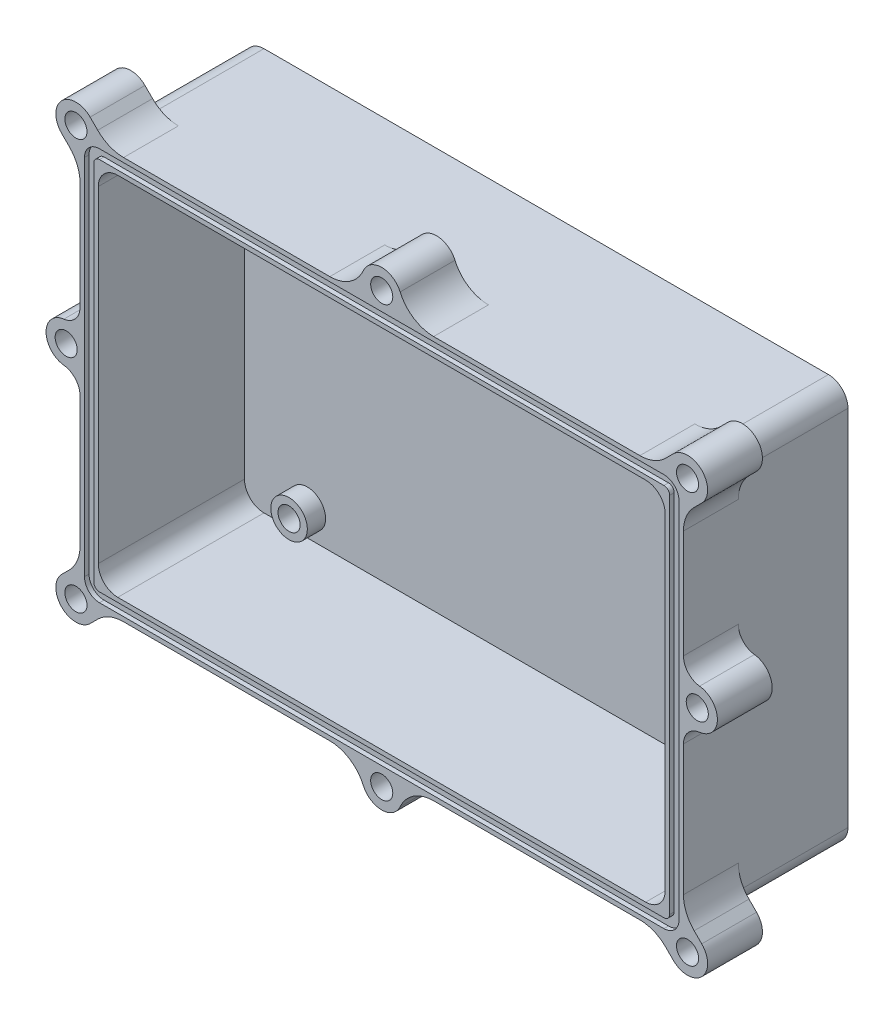
SolidWorks part; units mm, degrees
material "Custom Plastic"
ref_plane "X-Y Datum" through (0, 0, 0) normal (0, 0, 1) x (1, 0, 0)
ref_plane "X-Z Datum" through (0, 0, 0) normal (0, 1, 0) x (1, 0, 0)
ref_plane "Y-Z Datum" through (0, 0, 0) normal (1, 0, 0) x (0, 0, -1)
sketch "Sketch1" plane through (0, 0, 0) normal (0, 0, 1) x (1, 0, 0)
  line L1 (-82.55, 55) -> (82.55, 55)
  line L2 (-82.55, 55) -> (-82.55, -55)
  line L3 (-82.55, -55) -> (82.55, -55)
  line L4 (82.55, 55) -> (82.55, -55)
  line L5 (-82.55, 55) -> (82.55, -55) construction
  line L6 (-82.55, -55) -> (82.55, 55) construction
  point P0 (0, 0)
  dimension "D1" = 165.1
  dimension "D2" = 110
extrude "Boss-Extrude1" add sketch "Sketch1" along normal blind 45
shell "Shell1" thickness 5 removed face at (0, 0, 45)
fillet "Fillet1" radius 5.334 8 edges at (-77.55, -50, 25) (-82.55, -55, 22.5) (82.55, -55, 22.5) (77.55, -50, 25) (82.55, 55, 22.5) (77.55, 50, 25) (-82.55, 55, 22.5) (-77.55, 50, 25)
sketch "Sketch2" plane through (0, 0, 45) normal (0, 0, 1) x (1, 0, 0)
  line L20 (-77.216, -53.7827) -> (77.216, -53.7827)
  line L21 (81.3327, -49.666) -> (81.3327, 49.666)
  line L22 (77.216, 53.7827) -> (-77.216, 53.7827)
  line L23 (-81.3327, 49.666) -> (-81.3327, -49.666)
  line L24 (-77.216, -52.5) -> (77.216, -52.5)
  line L25 (80.05, -49.666) -> (80.05, 49.666)
  line L26 (77.216, 52.5) -> (-77.216, 52.5)
  line L27 (-80.05, 49.666) -> (-80.05, -49.666)
  line L28 (-77.216, -52.5) -> (77.216, -52.5) construction
  line L29 (80.05, -49.666) -> (80.05, 49.666) construction
  line L30 (77.216, 52.5) -> (-77.216, 52.5) construction
  line L31 (-80.05, 49.666) -> (-80.05, -49.666) construction
  line L32 (-78.7673, 49.666) -> (-78.7673, -49.666)
  line L33 (-77.216, -51.2173) -> (77.216, -51.2173)
  line L34 (78.7673, -49.666) -> (78.7673, 49.666)
  line L35 (77.216, 51.2173) -> (-77.216, 51.2173)
  arc A16 (77.216, -53.7827) -> (81.3327, -49.666) centre (77.216, -49.666) ccw
  arc A17 (81.3327, 49.666) -> (77.216, 53.7827) centre (77.216, 49.666) ccw
  arc A18 (-77.216, 53.7827) -> (-81.3327, 49.666) centre (-77.216, 49.666) ccw
  arc A19 (-81.3327, -49.666) -> (-77.216, -53.7827) centre (-77.216, -49.666) ccw
  arc A20 (-80.05, -49.666) -> (-77.216, -52.5) centre (-77.216, -49.666) ccw
  arc A21 (77.216, -52.5) -> (80.05, -49.666) centre (77.216, -49.666) ccw
  arc A22 (80.05, 49.666) -> (77.216, 52.5) centre (77.216, 49.666) ccw
  arc A23 (-77.216, 52.5) -> (-80.05, 49.666) centre (-77.216, 49.666) ccw
  arc A24 (-80.05, -49.666) -> (-77.216, -52.5) centre (-77.216, -49.666) ccw construction
  arc A25 (77.216, -52.5) -> (80.05, -49.666) centre (77.216, -49.666) ccw construction
  arc A26 (80.05, 49.666) -> (77.216, 52.5) centre (77.216, 49.666) ccw construction
  arc A27 (-77.216, 52.5) -> (-80.05, 49.666) centre (-77.216, 49.666) ccw construction
  arc A28 (-77.216, 51.2173) -> (-78.7673, 49.666) centre (-77.216, 49.666) ccw
  arc A29 (-78.7673, -49.666) -> (-77.216, -51.2173) centre (-77.216, -49.666) ccw
  arc A30 (77.216, -51.2173) -> (78.7673, -49.666) centre (77.216, -49.666) ccw
  arc A31 (78.7673, 49.666) -> (77.216, 51.2173) centre (77.216, 49.666) ccw
  dimension "D1" = 2.5
  dimension "D2" = 1.2827
  dimension "D3" = 1.2827
extrude "Cut-Extrude1" cut sketch "Sketch2" against normal blind 1.2446
sketch "Sketch3" plane through (0, 0, 45) normal (0, 0, 1) x (1, 0, 0)
  line L0 (77.216, 49.666) -> (80.9877, 53.4377)
  line L1 (80.9877, 53.4377) -> (83.6625, 56.1125)
  line L2 (79.7734, 60.0016) -> (74.7718, 55)
  line L3 (77.216, 55) -> (-77.216, 55) construction
  line L4 (82.55, -49.666) -> (82.55, 49.666) construction
  line L5 (82.55, -49.666) -> (82.55, 49.666)
  line L6 (77.216, 55) -> (-77.216, 55)
  line L7 (87.5516, 52.2234) -> (82.55, 47.2218)
  arc A0 (82.55, 49.666) -> (77.216, 55) centre (77.216, 49.666) ccw construction
  circle A1 centre (83.6625, 56.1125) radius 3.025
  circle A2 centre (83.6625, 56.1125) radius 5.5
  arc A3 (81.3327, 49.666) -> (77.216, 53.7827) centre (77.216, 49.666) ccw construction
  arc A4 (82.55, 49.666) -> (77.216, 55) centre (77.216, 49.666) ccw
  point P6 (87.5516, 52.2234)
  point P10 (80.1269, 52.5769)
  dimension "D1" = 6.05
  dimension "D2" = 11
  dimension "D3" = 5
extrude "Boss-Extrude2" add sketch "Sketch3" against normal blind 15
sketch "Sketch4" plane through (0, 0, 45) normal (0, 0, 1) x (1, 0, 0)
  line L0 (87.5516, 52.2234) -> (82.55, 47.2218) construction
  line L1 (79.7734, 60.0016) -> (74.7718, 55) construction
  line L2 (77.216, 49.666) -> (80.9877, 53.4377) construction
  line L3 (80.9877, 53.4377) -> (83.6625, 56.1125) construction
  line L4 (82.55, -49.666) -> (82.55, 49.666) construction
  line L5 (77.216, 55) -> (-77.216, 55) construction
  line L6 (87.5516, 52.2234) -> (82.55, 47.2218)
  line L7 (79.7734, 60.0016) -> (74.7718, 55)
  line L8 (77.216, 49.666) -> (80.9877, 53.4377)
  line L9 (80.9877, 53.4377) -> (83.6625, 56.1125)
  line L10 (82.55, -49.666) -> (82.55, 49.666)
  line L11 (77.216, 55) -> (-77.216, 55)
  arc A0 (82.55, 49.666) -> (77.216, 55) centre (77.216, 49.666) ccw construction
  circle A1 centre (83.6625, 56.1125) radius 5.5
  circle A2 centre (83.6625, 56.1125) radius 5.5
  circle A3 centre (83.6625, 56.1125) radius 3.025
  circle A4 centre (83.6625, 56.1125) radius 3.025
  arc A5 (82.55, 49.666) -> (77.216, 55) centre (77.216, 49.666) ccw
  dimension "D1" = 0
  dimension "D2" = 0
extrude "Cut-Extrude2" cut sketch "Sketch4" against normal blind 8
mirror "Mirror2" about plane through (0, 0, 0) normal (0, 1, 0) of "Cut-Extrude2", "Boss-Extrude2"
mirror "Mirror3" about plane through (0, 0, 0) normal (1, 0, 0) of "Mirror2", "Boss-Extrude2", "Cut-Extrude2"
fillet "Fillet3" radius 10 8 edges at (82.55, 47.2218, 37.5) (74.7718, 55, 37.5) (-74.7718, 55, 37.5) (-82.55, 47.2218, 37.5) (-82.55, -47.2218, 37.5) (-74.7718, -55, 37.5) (74.7718, -55, 37.5) (82.55, -47.2218, 37.5)
sketch "Sketch5" plane through (0, 0, 45) normal (0, 0, 1) x (1, 0, 0)
  line L1 (0, -55) -> (0, -58.7827)
  line L2 (-70.6297, -55) -> (70.6297, -55) construction
  line L3 (-77.216, -53.7827) -> (77.216, -53.7827) construction
  line L4 (-5.5, -58.7827) -> (-5.5, -55)
  line L5 (5.5, -58.7827) -> (5.5, -55)
  line L6 (-70.6297, -55) -> (70.6297, -55)
  circle A0 centre (0, -58.7827) radius 3.025
  circle A1 centre (0, -58.7827) radius 5.5
  dimension "D1" = 6.05
  dimension "D2" = 11
  dimension "D3" = 5
extrude "Boss-Extrude3" add sketch "Sketch5" against normal blind 15
sketch "Sketch6" plane through (0, 0, 45) normal (0, 0, 1) x (1, 0, 0)
  line L0 (-70.6297, -55) -> (70.6297, -55) construction
  line L1 (5.5, -58.7827) -> (5.5, -55) construction
  line L2 (-5.5, -58.7827) -> (-5.5, -55) construction
  line L3 (0, -55) -> (0, -58.7827) construction
  line L4 (-70.6297, -55) -> (70.6297, -55)
  line L5 (5.5, -58.7827) -> (5.5, -55)
  line L6 (-5.5, -58.7827) -> (-5.5, -55)
  line L7 (0, -55) -> (0, -58.7827)
  circle A1 centre (0, -58.7827) radius 5.5
  circle A2 centre (0, -58.7827) radius 5.5
  circle A3 centre (0, -58.7827) radius 3.025
  circle A4 centre (0, -58.7827) radius 3.025
  dimension "D1" = 0
  dimension "D2" = 0
extrude "Cut-Extrude3" cut sketch "Sketch6" against normal blind 8
mirror "Mirror10" about plane through (0, 0, 0) normal (0, 1, 0) of "Cut-Extrude3", "Boss-Extrude3"
fillet "Fillet5" radius 10 4 edges at (5.5, 55, 37.5) (-5.5, 55, 37.5) (-5.5, -55, 37.5) (5.5, -55, 37.5)
sketch "Sketch7" plane through (0, 0, 45) normal (0, 0, 1) x (1, 0, 0)
  line L0 (-82.55, 3.0797) -> (-86.3327, 3.0797)
  line L2 (-82.55, 43.0797) -> (-82.55, -43.0797) construction
  line L3 (-81.3327, 49.666) -> (-81.3327, -49.666) construction
  line L4 (-86.3327, 8.5797) -> (-82.55, 8.5797)
  line L5 (-86.3327, -2.4203) -> (-82.55, -2.4203)
  line L6 (-82.55, 43.0797) -> (-82.55, -43.0797)
  circle A0 centre (-86.3327, 3.0797) radius 3.025
  circle A1 centre (-86.3327, 3.0797) radius 5.5
  point P13 (-82.55, 0)
  point P14 (0, 0)
  dimension "D1" = 6.05
  dimension "D2" = 11
  dimension "D3" = 5
  dimension "D4" = 40
extrude "Boss-Extrude4" add sketch "Sketch7" against normal blind 15
sketch "Sketch8" plane through (0, 0, 45) normal (0, 0, 1) x (1, 0, 0)
  line L0 (-78.7673, 49.666) -> (-78.7673, -49.666) construction
  line L1 (-82.55, 43.0797) -> (-82.55, -43.0797) construction
  line L2 (-86.3327, -2.4203) -> (-82.55, -2.4203) construction
  line L3 (-86.3327, 8.5797) -> (-82.55, 8.5797) construction
  line L4 (-82.55, 3.0797) -> (-86.3327, 3.0797) construction
  line L5 (-82.55, 43.0797) -> (-82.55, -43.0797)
  line L6 (-86.3327, -2.4203) -> (-82.55, -2.4203)
  line L7 (-86.3327, 8.5797) -> (-82.55, 8.5797)
  line L8 (-82.55, 3.0797) -> (-86.3327, 3.0797)
  circle A1 centre (-86.3327, 3.0797) radius 5.5
  circle A2 centre (-86.3327, 3.0797) radius 5.5
  circle A3 centre (-86.3327, 3.0797) radius 3.025
  circle A4 centre (-86.3327, 3.0797) radius 3.025
  point P0 (-78.7673, 0)
  dimension "D1" = 0
  dimension "D2" = 0
extrude "Cut-Extrude4" cut sketch "Sketch8" against normal blind 8
mirror "Mirror11" about plane through (0, 0, 0) normal (1, 0, 0) of "Cut-Extrude4", "Boss-Extrude4"
fillet "Fillet6" radius 5 4 edges at (82.55, 8.5797, 37.5) (82.55, -2.4203, 37.5) (-82.55, 8.5797, 37.5) (-82.55, -2.4203, 37.5)
sketch "Sketch9" plane through (0, 0, 5) normal (0, 0, 1) x (1, 0, 0)
  circle A0 centre (-60.3534, 42.799) radius 3.025
  circle A1 centre (50.1366, 12.954) radius 3.025
  circle A2 centre (50.1366, -42.926) radius 3.025
  circle A3 centre (-60.3534, -42.926) radius 3.025
  circle A4 centre (-60.3534, -42.926) radius 5
  circle A5 centre (50.1366, -42.926) radius 5
  circle A6 centre (50.1366, 12.954) radius 5
  circle A7 centre (-60.3534, 42.799) radius 5
  point P0 (-60.3534, 42.799)
  point P1 (50.1366, 12.954)
  point P3 (50.1366, -42.926)
  point P5 (-60.3534, -42.926)
  dimension "D1" = 6.05
  dimension "D2" = 10
extrude "Boss-Extrude5" add sketch "Sketch9" along normal blind 5
